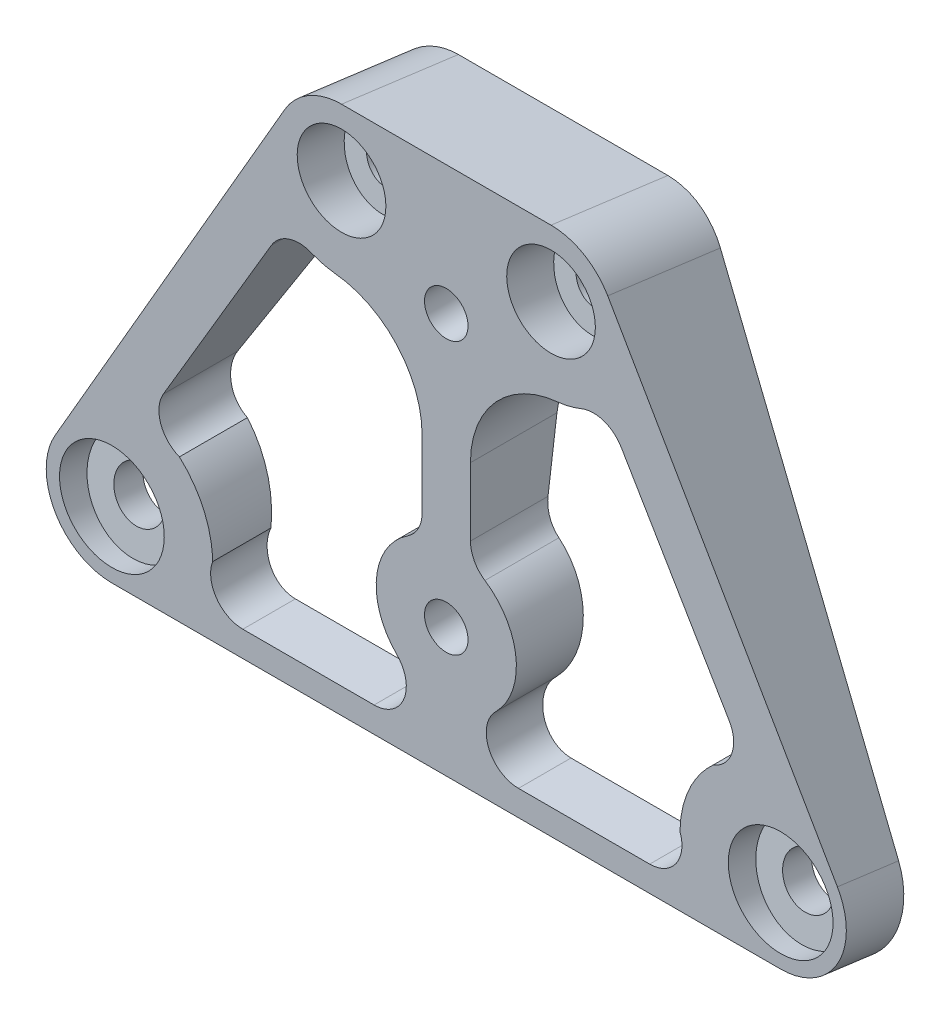
SolidWorks part; units mm, degrees
ref_plane "Front Plane" through (0, 0, 0) normal (0, 0, 1) x (1, 0, 0)
ref_plane "Top Plane" through (0, 0, 0) normal (0, 1, 0) x (1, 0, 0)
ref_plane "Right Plane" through (0, 0, 0) normal (1, 0, 0) x (0, 0, -1)
ref_axis "Axis1" through (-88.99, 0, 0) along (1, 0, 0)
ref_plane "Plane1" through (0, 0, 0) normal (0, 0.1305, 0.9914) x (1, 0, 0)
ref_plane "Plane2" through (0, 0, 3) normal (0, 0, 1) x (1, 0, 0)
sketch "Sketch1" plane through (0, 0, 0) normal (0, 0.1305, 0.9914) x (1, 0, 0)
  line L0 (-88.99, 0) -> (88.99, 0) construction
  line L2 (20.75, 4.075) -> (6.5, 28.5) construction
  line L3 (6.5, 28.5) -> (0, 28.5) construction
  line L4 (0, 28.5) -> (0, 0)
  line L5 (0, 0) -> (20.75, 0)
  line L6 (22.325, 4.075) -> (24.825, 4.075) construction
  line L7 (24.2698, 6.1285) -> (10.0198, 30.5535)
  line L8 (6.5, 32.575) -> (0, 32.575)
  line L9 (0, 32.575) -> (0, 28.5)
  circle A0 centre (6.5, 28.5) radius 1.375
  circle A1 centre (20.75, 4.075) radius 1.575
  arc A2 (24.2698, 6.1285) -> (20.75, 0) centre (20.75, 4.075) cw
  arc A3 (6.5, 32.575) -> (10.0198, 30.5535) centre (6.5, 28.5) cw
  dimension "D1" = 3.15
  dimension "D4" = 2.75
  dimension "D6" = 2.5
  dimension "D2" = 20.75
  dimension "D3" = 6.5
  dimension "D5" = 28.5
extrude "Boss-Extrude1" add sketch "Sketch1" along normal up to surface (6.778 mm away) up to plane "Plane2"
ref_plane "Plane3" through (0, 0.9547, 7.2519) normal (0, -0.1305, -0.9914) x (-1, 0, 0)
sketch "Sketch17" plane through (0, 0.9547, 7.2519) normal (0, -0.1305, -0.9914) x (-1, 0, 0)
  point P3 (-20.75, 4.075)
hole_wizard "CBORE for M3 SHCS1" positions "Sketch17" profile "Sketch18" counterbore size "M3" standard "ANSI Metric" end condition through all
sketch "Sketch18" plane through (20.75, 4.9949, 6.72) normal (1, 0, 0) x (0, -0.9914, 0.1305)
  line L0 (0, 0) -> (0, 11.53)
  line L1 (0, 11.53) -> (1.6, 11.53)
  line L3 (1.6, 11.53) -> (1.6, 5.5)
  line L4 (1.6, 5.5) -> (3.25, 5.5)
  line L5 (3.25, 5.5) -> (3.25, 0)
  line L7 (3.25, 0) -> (0, 0)
  line L11 (0, -6.35) -> (0, 107.95) construction
  dimension "Thru Hole Dia." = 3.2
  dimension "Thru Hole Depth" = 11.53
  dimension "C'Bore Dia." = 6.5
  dimension "C'Bore Depth" = 5.5
sketch "Sketch26" plane through (0, 0.9547, 7.2519) normal (0, -0.1305, -0.9914) x (-1, 0, 0)
  point P0 (-6.5, 28.5)
hole_wizard "CBORE for M2.5 SHCS2" positions "Sketch26" profile "Sketch25" counterbore size "M2.5" standard "ANSI Metric" end condition through all
sketch "Sketch25" plane through (6.5, 29.2109, 3.5319) normal (1, 0, 0) x (0, -0.9914, 0.1305)
  line L0 (0, 0) -> (0, 11.53)
  line L1 (0, 11.53) -> (1.35, 11.53)
  line L3 (1.35, 11.53) -> (1.35, 3.5)
  line L4 (1.35, 3.5) -> (2.75, 3.5)
  line L5 (2.75, 3.5) -> (2.75, 0)
  line L7 (2.75, 0) -> (0, 0)
  line L11 (0, -6.35) -> (0, 107.95) construction
  dimension "Thru Hole Dia." = 2.7
  dimension "Thru Hole Depth" = 11.53
  dimension "C'Bore Dia." = 5.5
  dimension "C'Bore Depth" = 3.5
mirror "Mirror1" about plane through (0, 0, 0) normal (1, 0, 0) of bodies 113 104
sketch "Sketch19" plane through (0, 0, 3) normal (0, 0, 1) x (1, 0, 0)
  line L0 (0, 0.395) -> (0, 8.395) construction
  line L1 (-20.75, 0.395) -> (20.75, 0.395) construction
  line L2 (0, 8.395) -> (0, 25.251) construction
  line L3 (0, 25.251) -> (0, 33.251) construction
  line L4 (6.5, 33.251) -> (-6.5, 33.251) construction
  dimension "D1" = 8
ref_plane "Plane4" through (0, 0, -4.2519) normal (0, 0, 1) x (1, 0, 0)
sketch "Sketch22" plane through (0, 0, -4.2519) normal (0, 0, 1) x (1, 0, 0)
  point P0 (0, 25.251)
  point P3 (0, 8.395)
hole_wizard "CBORE for M2.5 SHCS1" positions "Sketch22" profile "Sketch21" counterbore size "M2.5" standard "ANSI Metric" end condition through all
sketch "Sketch21" plane through (0, 25.251, -4.2519) normal (1, 0, 0) x (0, 1, 0)
  line L0 (0, 0) -> (0, 7.2519)
  line L1 (0, 7.2519) -> (1.35, 7.2519)
  line L3 (1.35, 7.2519) -> (1.35, 5)
  line L4 (1.35, 5) -> (2.75, 5)
  line L5 (2.75, 5) -> (2.75, 0)
  line L7 (2.75, 0) -> (0, 0)
  line L11 (0, -6.35) -> (0, 107.95) construction
  dimension "Thru Hole Dia." = 2.7
  dimension "Thru Hole Depth" = 7.2519
  dimension "C'Bore Dia." = 5.5
  dimension "C'Bore Depth" = 5
sketch "Sketch23" plane through (0, 0, 3) normal (0, 0, 1) x (1, 0, 0)
  line L0 (12.6238, 1.9752) -> (4.4802, 1.9752)
  line L1 (-20.75, 0.4752) -> (20.75, 0.4752) construction
  line L2 (1.5, 13.7735) -> (1.5, 17.9854)
  line L5 (0, 8.4752) -> (0, 25.4562) construction
  line L8 (6.5, 30.4562) -> (-6.5, 30.4562)
  line L9 (-7.4204, 29.9117) -> (-21.6704, 5.1822)
  line L10 (-20.75, 3.4752) -> (20.75, 3.4752)
  line L11 (21.6704, 5.1822) -> (7.4204, 29.9117)
  line L15 (17.5548, 12.1492) -> (10.8536, 23.4927)
  arc A6 (16.5603, 9.2689) -> (17.5548, 12.1492) centre (15.8328, 11.1319) ccw
  arc A7 (12.6238, 1.9752) -> (14.5003, 4.6669) centre (12.6238, 3.9752) ccw
  arc A8 (2.3976, 12.1047) -> (1.5, 13.7735) centre (3.5, 13.7735) cw
  arc A10 (4.4802, 1.9752) -> (3.0691, 5.3925) centre (4.4802, 3.9752) cw
  circle A11 centre (0, 8.4752) radius 4.35
  arc A12 (3.0691, 5.3925) -> (2.3976, 12.1047) centre (0, 8.4752) ccw
  arc A14 (1.5, 17.9854) -> (6.9402, 23.9592) centre (7.5, 17.9854) cw
  arc A16 (10.8536, 23.4927) -> (8.3486, 24.3158) centre (9.1316, 22.4755) ccw
  spline S0 degree 3 poles (191.6747, -949.7097) (35.9737, -102.1442) (2.7467, 33.0725) (-6.866, 30.3933) (-6.9529, 30.3558) (-12.7663, 26.8794) (14.161, -31.4536) (769.274, 659.7717) knots -26.233599 -26.233599 -26.233599 -26.233599 0.25 0.25 0.5 0.5 18.469193 18.469193 18.469193 18.469193 only from (-6.5, 30.4562) to (-7.4204, 29.9117)
  spline S1 degree 3 poles (926.1396, -313.6531) (90.5364, -16.2558) (-19.2531, 14.0632) (-21.8086, 4.8199) (-21.8228, 4.7218) (-21.8267, 4.5279) (-21.8165, 4.4294) (-21.7724, 4.2399) (-21.739, 4.1489) (-21.6482, 3.9748) (-21.5925, 3.895) (-21.4615, 3.7515) (-21.3854, 3.6876) (-21.2214, 3.5844) (-21.1309, 3.5434) (-12.0573, 0.9015) (20.253, 120.9235) (193.2166, 980.3011) knots -12.07462 -12.07462 -12.07462 -12.07462 0.125 0.125 0.25 0.25 0.375 0.375 0.5 0.5 0.625 0.625 0.75 0.75 0.875 0.875 12.906827 12.906827 12.906827 12.906827 only from (-21.6704, 5.1822) to (-20.75, 3.4752)
  spline S2 degree 3 poles (-178.1996, 983.4839) (-23.5324, 143.5098) (11.2764, 0.6713) (21.1315, 3.5436) (21.2212, 3.5843) (21.4677, 3.7394) (21.604, 3.8899) (21.7835, 4.2345) (21.8286, 4.4296) (21.6829, 11.7517) (-43.377, 16.2041) (-34.662, -993.2018) knots -12.909004 -12.909004 -12.909004 -12.909004 0.125 0.125 0.25 0.25 0.5 0.5 0.75 0.75 9.895674 9.895674 9.895674 9.895674 only from (20.75, 3.4752) to (21.6704, 5.1822)
  spline S3 degree 3 poles (-732.279, -643.0255) (-258.817, -231.8914) (18.905, 18.1778) (7.1871, 30.2012) (7.1126, 30.2603) (6.9532, 30.3556) (6.8658, 30.3934) (-2.2368, 32.9303) (-33.9648, -87.629) (-202.1485, -947.511) knots -44.490232 -44.490232 -44.490232 -44.490232 0.25 0.25 0.5 0.5 0.75 0.75 25.858278 25.858278 25.858278 25.858278 only from (7.4204, 29.9117) to (6.5, 30.4562)
  spline S4 degree 3 poles (6.185, 24.5461) (6.815, 24.5461) (7.1246, 24.5774) (7.7337, 24.6997) (8.0363, 24.7924) (8.6126, 25.0338) (8.8857, 25.1815) (9.4025, 25.5303) (9.6466, 25.7329) (10.0839, 26.175) (10.2801, 26.4162) (10.6263, 26.9397) (10.7727, 27.2172) (11.0083, 27.7918) (11.099, 28.0932) (11.2199, 28.7081) (11.2499, 29.0173) (11.2501, 29.6393) (11.2195, 29.9552) (11.0991, 30.5665) (11.0101, 30.8639) (10.7736, 31.4421) (10.6256, 31.7218) (10.2832, 32.2401) (10.0876, 32.4819) (9.6454, 32.9294) (9.405, 33.1285) (9.0193, 33.3894) (8.8863, 33.4701) (8.6114, 33.6189) (8.4688, 33.6872) (8.0361, 33.8686) (7.7392, 33.9596) (7.1288, 34.0829) (6.8129, 34.1146) (6.1906, 34.1148) (5.8814, 34.0844) (5.2671, 33.9615) (4.966, 33.8691) (4.3929, 33.6296) (4.1165, 33.4808) (3.5963, 33.1298) (3.3571, 32.9313) (2.9193, 32.4895) (2.7192, 32.2434) (2.3752, 31.7235) (2.2298, 31.4491) (1.9924, 30.8713) (1.9014, 30.5682) (1.781, 29.9587) (1.7503, 29.6491) (1.7497, 29.0198) (1.7801, 28.7094) (1.8994, 28.1) (1.9897, 27.7974) (2.2265, 27.2184) (2.3715, 26.9438) (2.7141, 26.4242) (2.914, 26.1775) (3.3514, 25.7346) (3.59, 25.536) (4.108, 25.1851) (4.3857, 25.0348) (4.9582, 24.7944) (5.2566, 24.7021) (5.8734, 24.5774) (6.185, 24.5461) (6.815, 24.5461) (7.1246, 24.5774) knots -0.03125 -0.03125 0 0 0.03125 0.03125 0.0625 0.0625 0.09375 0.09375 0.125 0.125 0.15625 0.15625 0.1875 0.1875 0.21875 0.21875 0.25 0.25 0.28125 0.28125 0.3125 0.3125 0.34375 0.34375 0.375 0.375 0.40625 0.40625 0.421875 0.421875 0.4375 0.4375 0.46875 0.46875 0.5 0.5 0.53125 0.53125 0.5625 0.5625 0.59375 0.59375 0.625 0.625 0.65625 0.65625 0.6875 0.6875 0.71875 0.71875 0.75 0.75 0.78125 0.78125 0.8125 0.8125 0.84375 0.84375 0.875 0.875 0.90625 0.90625 0.9375 0.9375 0.96875 0.96875 1 1 1.03125 1.03125 1.0625 only from (6.5, 24.5461) to (6.5, 24.5461)
  spline S5 degree 3 poles (6.9402, 23.9592) (7.1436, 23.9818) (7.3447, 24.016) (7.8163, 24.1245) (8.0871, 24.2099) (8.3486, 24.3158) knots 0.012995 0.012995 0.012995 0.012995 0.03125 0.03125 0.056301 0.056301 0.056301 0.056301
  spline S10 degree 3 poles (20.3357, -1.6896) (21.1643, -1.6896) (21.5716, -1.6485) (22.1724, -1.5279) (22.371, -1.4778) (22.7648, -1.3574) (22.9603, -1.2867) (23.5289, -1.0487) (23.8882, -0.8547) (24.5681, -0.3963) (24.8894, -0.13) (25.4649, 0.4513) (25.7231, 0.7683) (26.0648, 1.2845) (26.1706, 1.4628) (26.3624, 1.8254) (26.5358, 2.1956) (26.6726, 2.5811) (26.7908, 2.9742) (26.8409, 3.1757) (26.9604, 3.7824) (26.9998, 4.1891) (27.0002, 5.0072) (26.9598, 5.4226) (26.8014, 6.2267) (26.6841, 6.6179) (26.4506, 7.1881) (26.3625, 7.3764) (26.1699, 7.7404) (26.0653, 7.9165) (25.7273, 8.4276) (25.4698, 8.7455) (24.8878, 9.3337) (24.5716, 9.5954) (24.064, 9.9383) (23.889, 10.0445) (23.5273, 10.2401) (23.3397, 10.3298) (22.7705, 10.5681) (22.3799, 10.6878) (21.5771, 10.8497) (21.1615, 10.8913) (20.343, 10.8916) (19.9364, 10.8517) (19.3303, 10.7305) (19.1288, 10.6797) (18.7361, 10.5595) (18.3514, 10.4206) (17.9823, 10.2448) (17.6211, 10.0504) (17.4436, 9.9432) (16.9303, 9.5972) (16.6155, 9.3363) (16.0394, 8.7556) (15.7759, 8.4319) (15.3232, 7.7483) (15.1318, 7.3875) (14.8973, 6.8176) (14.8277, 6.6218) (14.7091, 6.2274) (14.6597, 6.0286) (14.5409, 5.4273) (14.5004, 5.0202) (14.4996, 4.1926) (14.5396, 3.7842) (14.6575, 3.183) (14.7065, 2.9843) (14.8243, 2.5904) (14.8936, 2.3944) (15.1274, 1.8233) (15.3183, 1.4622) (15.7692, 0.7789) (16.0323, 0.4545) (16.6079, -0.1276) (16.9219, -0.3888) (17.4332, -0.7347) (17.611, -0.8426) (17.9725, -1.0381) (18.1571, -1.1264) (18.722, -1.3634) (19.1145, -1.4846) (19.9258, -1.6485) (20.3357, -1.6896) (21.1643, -1.6896) (21.5716, -1.6485) knots -0.03125 -0.03125 0 0 0.03125 0.03125 0.046875 0.046875 0.0625 0.0625 0.09375 0.09375 0.125 0.125 0.15625 0.15625 0.171875 0.171875 0.1875 0.203125 0.203125 0.21875 0.21875 0.25 0.25 0.28125 0.28125 0.3125 0.3125 0.328125 0.328125 0.34375 0.34375 0.375 0.375 0.40625 0.40625 0.421875 0.421875 0.4375 0.4375 0.46875 0.46875 0.5 0.5 0.53125 0.53125 0.546875 0.546875 0.5625 0.578125 0.578125 0.59375 0.59375 0.625 0.625 0.65625 0.65625 0.6875 0.6875 0.703125 0.703125 0.71875 0.71875 0.75 0.75 0.78125 0.78125 0.796875 0.796875 0.8125 0.8125 0.84375 0.84375 0.875 0.875 0.90625 0.90625 0.921875 0.921875 0.9375 0.9375 0.96875 0.96875 1 1 1.03125 1.03125 1.046875 only from (20.75, -1.6896) to (20.75, -1.6896)
  spline S11 degree 3 poles (16.5603, 9.2689) (16.4809, 9.1966) (16.4032, 9.1223) (16.0394, 8.7556) (15.7759, 8.4319) (15.3232, 7.7483) (15.1318, 7.3875) (14.8973, 6.8176) (14.8277, 6.6218) (14.7091, 6.2274) (14.6597, 6.0286) (14.5447, 5.4469) (14.5044, 5.0599) (14.5003, 4.6669) knots 0.61678 0.61678 0.61678 0.61678 0.625 0.625 0.65625 0.65625 0.6875 0.6875 0.703125 0.703125 0.71875 0.71875 0.748474 0.748474 0.748474 0.748474
  point P22 (5.7097, 23.9387)
  dimension "D7" = 1.5
  dimension "D8" = 2
  dimension "D9" = 2
  dimension "D10" = 6
  dimension "D3" = 2
  dimension "D2" = 2
  dimension "D1" = 3
  dimension "D6" = 1.5
  dimension "D4" = 3
  dimension "D5" = 3
extrude "Cut-Extrude2" cut sketch "Sketch23" against normal through all
mirror "Mirror2" about plane through (0, 0, 0) normal (1, 0, 0) of "Cut-Extrude2"
